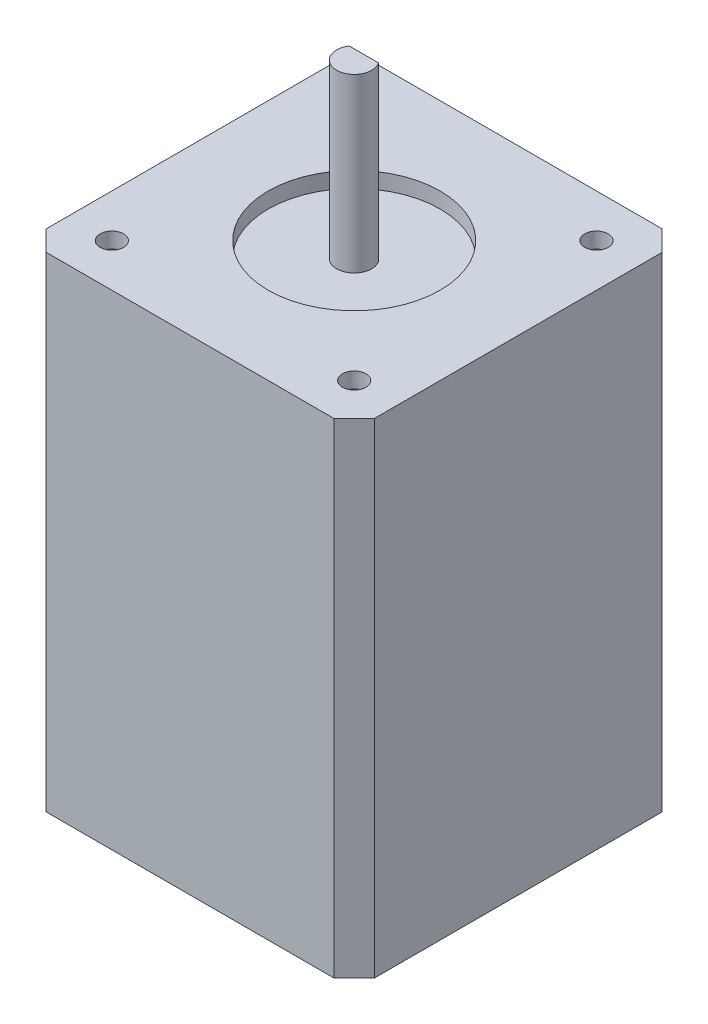
SolidWorks part; units mm, degrees
ref_plane "前视基准面" through (0, 0, 0) normal (0, 0, 1) x (1, 0, 0)
ref_plane "上视基准面" through (0, 0, 0) normal (0, 1, 0) x (1, 0, 0)
ref_plane "右视基准面" through (0, 0, 0) normal (1, 0, 0) x (0, 0, -1)
other "Configuration Table"
sketch "草图1" plane through (0, 0, 0) normal (0, 1, 0) x (1, 0, 0)
  line L0 (-21, 18.3155) -> (-18.3155, 21)
  line L1 (-21, 21) -> (21, 21)
  line L2 (-21, 21) -> (-21, -21)
  line L3 (-21, -21) -> (21, -21)
  line L4 (21, 21) -> (21, -21)
  line L5 (-21, 21) -> (21, -21) construction
  line L6 (-21, -21) -> (21, 21) construction
  line L7 (18.3588, 21) -> (21, 18.3588)
  line L8 (-21, -18.4021) -> (-18.4021, -21)
  line L9 (21, -18.4021) -> (18.4021, -21)
  line L10 (-1.8708, 1.25) -> (1.8708, 1.25)
  circle A0 centre (-15.5, 15.5) radius 1.5
  circle A1 centre (15.5, 15.5) radius 1.5
  circle A2 centre (-15.5, -15.5) radius 1.5
  circle A3 centre (15.5, -15.5) radius 1.5
  circle A4 centre (0, 0) radius 11
  circle A5 centre (0, 0) radius 2.25
  point P0 (0, 0)
  dimension "D3" = 3
  dimension "D4" = 3
  dimension "D5" = 3
  dimension "D6" = 3
  dimension "D7" = 31
  dimension "D9" = 1.25
  dimension "D10" = 4.5
  dimension "D1" = 42
  dimension "D2" = 42
  dimension "D8" = 31
extrude "凸台-拉伸1" add sketch "草图1" along normal blind 2 and the other way blind 60 contours L9 L4 L7 L1 L0 L2 L8 L3 A4 A3 A2 A1 A0 region at (-19.2377, 0, -19.2377)
extrude "凸台-拉伸2" add sketch "草图1<3>" along normal blind 22 separate body contours L10 A5 region at (0, 0, 0.3289)
sketch "草图1<3>" plane through (0, 0, 0) normal (0, 1, 0) x (1, 0, 0) same geometry as "草图1"
sketch "草图2" plane through (0, -60, 0) normal (0, -1, 0) x (1, 0, 0)
  circle A0 centre (0, 0) radius 11
  circle A1 centre (-15.5, 15.5) radius 1.5
  circle A2 centre (15.5, 15.5) radius 1.5
  circle A3 centre (-15.5, -15.5) radius 1.5
  circle A4 centre (15.5, -15.5) radius 1.5
extrude "凸台-拉伸3" add sketch "草图2" against normal blind 60
